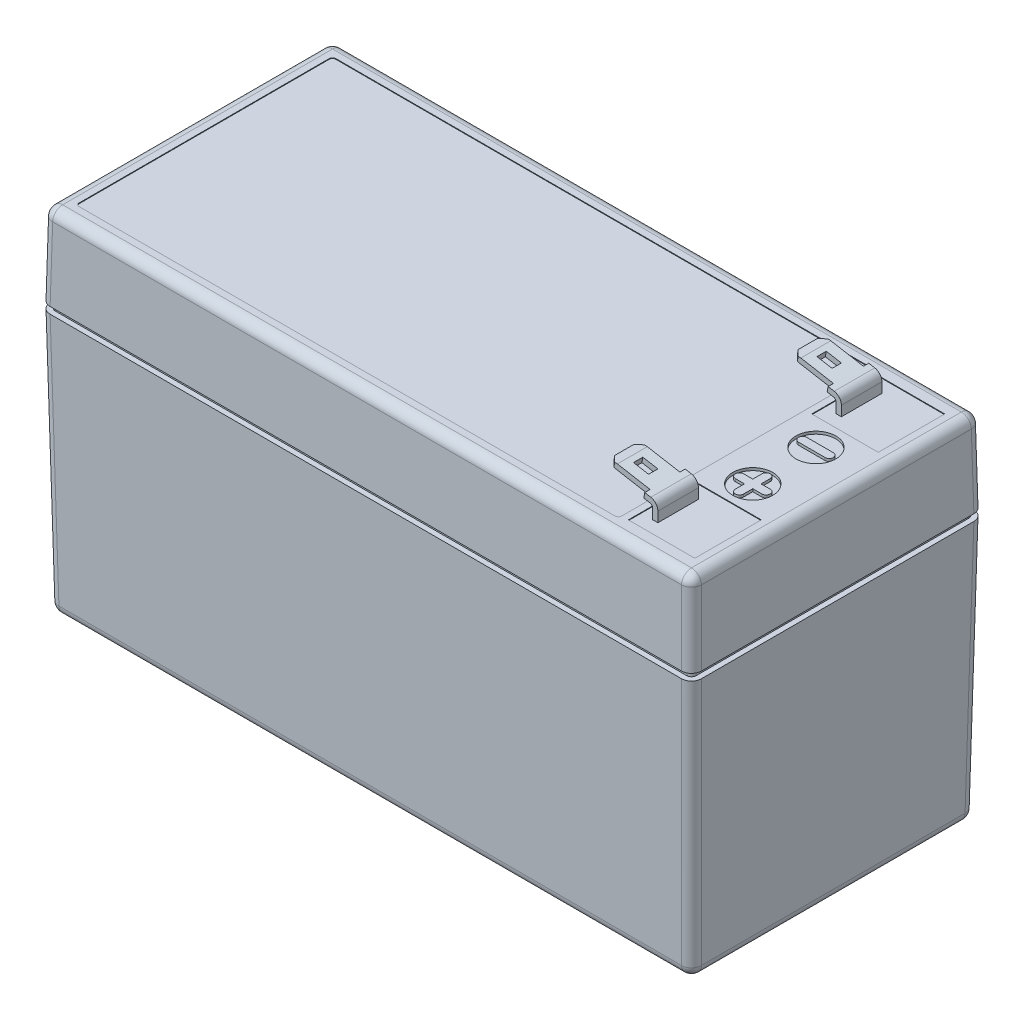
SolidWorks part; units mm, degrees
note: The reader was unsure of these and kept them because the rebuilt part matched: shared geometry of "Sketch4<3>".
ref_plane "Front Plane" through (0, 0, 0) normal (0, 0, 1) x (1, 0, 0)
ref_plane "Top Plane" through (0, 0, 0) normal (0, 1, 0) x (1, 0, 0)
ref_plane "Right Plane" through (0, 0, 0) normal (1, 0, 0) x (0, 0, -1)
sketch "Sketch1" plane through (0, 0, 0) normal (0, 1, 0) x (1, 0, 0)
  line L1 (-49, 22) -> (49, 22)
  line L2 (-49, 22) -> (-49, -22)
  line L3 (-49, -22) -> (49, -22)
  line L4 (49, 22) -> (49, -22)
  point P4 (-49, 0)
  point P6 (0, 22)
  dimension "D1" = 98
  dimension "D2" = 44
extrude "Extrude1" add sketch "Sketch1" along normal blind 13 draft 1 and the other way blind 40 draft 1
fillet "Fillet1" radius 1.5 16 edges at (48.7731, 13, 0) (-48.3018, -40, 0) (-48.6509, -20, 21.6509) (0, -40, -21.3018) (0, 13, -21.7731) (-48.6509, -20, -21.6509) (48.3018, -40, 0) (48.6509, -20, -21.6509) (0, -40, 21.3018) (48.6509, -20, 21.6509) (-48.7731, 13, 0) (0, 13, 21.7731) (-48.8865, 6.5, -21.8865) (48.8865, 6.5, -21.8865) (48.8865, 6.5, 21.8865) (-48.8865, 6.5, 21.8865)
sketch3d "3DSketch1"
  line L0 (-49, 0, -20.5002) -> (-49, 0, 20.5002) construction
  line L1 (47.5002, 0, -22) -> (-47.5002, 0, -22) construction
  line L2 (-47.5002, 0, 22) -> (47.5002, 0, 22) construction
  line L3 (49, 0, 20.5002) -> (49, 0, -20.5002) construction
  line L4 (-49, 0, -20.5002) -> (-49, 0, 20.5002)
  line L5 (47.5002, 0, -22) -> (-47.5002, 0, -22)
  line L6 (-47.5002, 0, 22) -> (47.5002, 0, 22)
  line L7 (49, 0, 20.5002) -> (49, 0, -20.5002)
  spline S0 degree 3 poles (-49, 0, 20.5002) (-49, 0, 21.3788) (-48.3788, 0, 22) (-47.5002, 0, 22) knots 0 0 0 0 1 1 1 1 weights 1 0.80481 0.80481 1 construction
  spline S1 degree 3 poles (-47.5002, 0, -22) (-48.3788, 0, -22) (-49, 0, -21.3788) (-49, 0, -20.5002) knots 0 0 0 0 1 1 1 1 weights 1 0.80481 0.80481 1 construction
  spline S2 degree 3 poles (49, 0, -20.5002) (49, 0, -21.3788) (48.3788, 0, -22) (47.5002, 0, -22) knots 0 0 0 0 1 1 1 1 weights 1 0.80481 0.80481 1 construction
  spline S3 degree 3 poles (47.5002, 0, 22) (48.3788, 0, 22) (49, 0, 21.3788) (49, 0, 20.5002) knots 0 0 0 0 1 1 1 1 weights 1 0.80481 0.80481 1 construction
  spline S4 degree 3 poles (-49, 0, 20.5002) (-49, 0, 21.3788) (-48.3788, 0, 22) (-47.5002, 0, 22) knots 0 0 0 0 1 1 1 1 weights 1 0.80481 0.80481 1
  spline S5 degree 3 poles (-47.5002, 0, -22) (-48.3788, 0, -22) (-49, 0, -21.3788) (-49, 0, -20.5002) knots 0 0 0 0 1 1 1 1 weights 1 0.80481 0.80481 1
  spline S6 degree 3 poles (49, 0, -20.5002) (49, 0, -21.3788) (48.3788, 0, -22) (47.5002, 0, -22) knots 0 0 0 0 1 1 1 1 weights 1 0.80481 0.80481 1
  spline S7 degree 3 poles (47.5002, 0, 22) (48.3788, 0, 22) (49, 0, 21.3788) (49, 0, 20.5002) knots 0 0 0 0 1 1 1 1 weights 1 0.80481 0.80481 1
sketch "Sketch3" plane through (0, 0, 0) normal (1, 0, 0) x (0, 0, -1)
  line L1 (22.4972, 0.5) -> (21.2, 0.5)
  line L2 (22.4972, 0.5) -> (22.4972, -0.5)
  line L3 (22.4972, -0.5) -> (21.2, -0.5)
  line L4 (21.2, 0.5) -> (21.2, -0.5)
  point P4 (21.2, 0)
  dimension "D1" = 1
  dimension "D2" = 0.8
sweep "Cut-Sweep1" cut profiles "Sketch3" path "3DSketch1"
sketch "Sketch4" plane through (0, -40, 0) normal (0, -1, 0) x (1, 0, 0)
  line L0 (46.8278, 19.8278) -> (-46.8278, 19.8278) construction
  line L1 (-44.6278, 17.6278) -> (-38.6278, 17.6278)
  line L2 (-44.6278, 17.6278) -> (-44.6278, 11.6278)
  line L3 (-44.6278, 11.6278) -> (-42.6278, 11.6278)
  line L4 (-38.6278, 17.6278) -> (-38.6278, 15.6278)
  line L5 (-42.6278, 15.6278) -> (-38.6278, 15.6278)
  line L6 (-42.6278, 15.6278) -> (-42.6278, 11.6278)
  line L7 (-46.8278, 19.8278) -> (-46.8278, -19.8278) construction
  line L8 (0, 11.6278) -> (0, -9.5326) construction
  line L9 (-20.3603, 0) -> (14.1633, 0) construction
  line L10 (42.6278, 15.6278) -> (42.6278, 11.6278)
  line L11 (42.6278, 15.6278) -> (38.6278, 15.6278)
  line L12 (38.6278, 17.6278) -> (38.6278, 15.6278)
  line L13 (44.6278, 11.6278) -> (42.6278, 11.6278)
  line L14 (44.6278, 17.6278) -> (44.6278, 11.6278)
  line L15 (44.6278, 17.6278) -> (38.6278, 17.6278)
  line L16 (44.6278, -17.6278) -> (38.6278, -17.6278)
  line L17 (44.6278, -17.6278) -> (44.6278, -11.6278)
  line L18 (44.6278, -11.6278) -> (42.6278, -11.6278)
  line L19 (38.6278, -17.6278) -> (38.6278, -15.6278)
  line L20 (42.6278, -15.6278) -> (38.6278, -15.6278)
  line L21 (42.6278, -15.6278) -> (42.6278, -11.6278)
  line L22 (-42.6278, -15.6278) -> (-42.6278, -11.6278)
  line L23 (-42.6278, -15.6278) -> (-38.6278, -15.6278)
  line L24 (-38.6278, -17.6278) -> (-38.6278, -15.6278)
  line L25 (-44.6278, -11.6278) -> (-42.6278, -11.6278)
  line L26 (-44.6278, -17.6278) -> (-44.6278, -11.6278)
  line L27 (-44.6278, -17.6278) -> (-38.6278, -17.6278)
  line L28 (-15, -1.75) -> (15, -1.75) construction
  line L29 (-18.5, 1.75) -> (-15, 1.75)
  line L30 (-18.5, 1.75) -> (-18.5, -1.75)
  line L31 (-18.5, -1.75) -> (-15, -1.75)
  line L32 (-15, 1.75) -> (-15, -1.75)
  line L33 (15, 1.75) -> (18.5, 1.75)
  line L34 (15, 1.75) -> (15, -1.75)
  line L35 (15, -1.75) -> (18.5, -1.75)
  line L36 (18.5, 1.75) -> (18.5, -1.75)
  point P41 (15, 0)
  point P42 (0, -1.75)
  dimension "D1" = 2
  dimension "D2" = 2
  dimension "D3" = 6
  dimension "D4" = 6
  dimension "D5" = 2.2
  dimension "D6" = 2.2
  dimension "D7" = 3.5
  dimension "D8" = 3.5
  dimension "D9" = 30
extrude "Extrude3" add sketch "Sketch4" along normal blind 0.3 contours L27 L24 L23 L22 L25 L26 | L3 L6 L5 L4 L1 L2 | L18 L21 L20 L19 L16 L17 | L15 L12 L11 L10 L13 L14
extrude "Cut-Extrude1" cut sketch "Sketch4<3>" against normal blind 0.5 contours L31 L32 L29 L30 | L35 L36 L33 L34
sketch "Sketch4<3>" plane through (0, -40, 0) normal (0, -1, 0) x (1, 0, 0) same geometry as "Sketch4"
sketch "Sketch5" plane through (0, 13, 0) normal (0, 1, 0) x (-1, 0, 0)
  line L0 (-47.299, -20.299) -> (47.299, -20.299) construction
  line L1 (46.299, 19.299) -> (-35.299, 19.299)
  line L2 (46.299, 19.299) -> (46.299, -19.299)
  line L3 (46.299, -19.299) -> (-35.299, -19.299)
  line L4 (-35.299, 19.299) -> (-35.299, -19.299)
  line L5 (47.299, 20.299) -> (-47.299, 20.299) construction
  line L6 (47.299, -20.299) -> (47.299, 20.299) construction
  line L7 (-47.299, 20.299) -> (-47.299, -20.299) construction
  dimension "D1" = 1
  dimension "D2" = 1
  dimension "D3" = 1
  dimension "D4" = 12
extrude "Cut-Extrude2" cut sketch "Sketch5" against normal blind 0.1
fillet "Fillet2" radius 0.5 4 edges at (35.299, 12.95, 19.299) (35.299, 12.95, -19.299) (-46.299, 12.95, 19.299) (-46.299, 12.95, -19.299)
sketch "Sketch6" plane through (0, 13, 0) normal (0, 1, 0) x (-1, 0, 0)
  line L0 (47.299, 20.299) -> (-47.299, 20.299) construction
  line L1 (-36.299, 18.799) -> (-46.299, 18.799)
  line L2 (-36.299, 18.799) -> (-36.299, 8.799)
  line L3 (-36.299, 8.799) -> (-46.299, 8.799)
  line L4 (-46.299, 18.799) -> (-46.299, 8.799)
  line L5 (-36.299, -8.799) -> (-46.299, -8.799)
  line L6 (-36.299, -8.799) -> (-36.299, -18.799)
  line L7 (-36.299, -18.799) -> (-46.299, -18.799)
  line L8 (-46.299, -8.799) -> (-46.299, -18.799)
  line L9 (-47.299, -20.299) -> (47.299, -20.299) construction
  line L10 (-47.299, 20.299) -> (-47.299, -20.299) construction
  dimension "D1" = 1.5
  dimension "D2" = 1.5
  dimension "D3" = 10
  dimension "D4" = 10
  dimension "D5" = 1
extrude "Cut-Extrude3" cut sketch "Sketch6" against normal blind 0.1
sketch "Sketch7" plane through (0, 0, 0) normal (0, 0, 1) x (1, 0, 0)
  line L0 (38.799, 11.5262) -> (38.799, 15.5)
  line L1 (47.299, 11.5262) -> (-47.299, 11.5262) construction
  line L2 (38.799, 15.5) -> (30.7236, 16.9239)
  line L3 (-47.299, 13) -> (47.299, 13) construction
  dimension "D1" = 2.5
  dimension "D2" = 2.5
  dimension "D3" = 8.2
  dimension "D4" = 100
extrude "Extrude-Thin1" add sketch "Sketch7" along normal blind 6.1 from offset 10.75 thin thin type one direction reverse wall 0.8
sketch "Sketch8" plane through (3.8206, 21.6676, 0) normal (0.1736, 0.9848, 0) x (-0.9848, 0.1736, 0)
  line L0 (-33.5075, 8.799) -> (-33.5075, 18.799) construction
  line L1 (-33.5075, 16.85) -> (-27.318, 16.85)
  line L2 (-33.5075, 16.85) -> (-33.5075, 16.05)
  line L3 (-33.5075, 16.05) -> (-27.318, 16.05)
  line L4 (-27.318, 16.85) -> (-27.318, 16.05)
  line L5 (-35.518, 16.85) -> (-27.318, 16.85) construction
  line L6 (-27.318, 16.85) -> (-27.318, 10.75) construction
  line L7 (-35.518, 10.75) -> (-27.318, 10.75) construction
  line L8 (-33.4901, 10.75) -> (-27.318, 10.75)
  line L9 (-33.4901, 10.75) -> (-33.4901, 11.55)
  line L10 (-33.4901, 11.55) -> (-27.318, 11.55)
  line L11 (-27.318, 10.75) -> (-27.318, 11.55)
  line L12 (-33.4901, 8.799) -> (-33.4901, 18.799) construction
  line L13 (-33.5075, 16.05) -> (-33.4988, 13.8) construction
  line L14 (-31.7062, 14.5) -> (-29.4062, 14.5)
  line L15 (-31.7062, 14.5) -> (-31.7062, 13.1)
  line L16 (-31.7062, 13.1) -> (-29.4062, 13.1)
  line L17 (-29.4062, 14.5) -> (-29.4062, 13.1)
  line L18 (-33.4988, 13.8) -> (-33.4901, 11.55) construction
  point P25 (-31.7062, 13.8)
  dimension "D1" = 0.8
  dimension "D2" = 0.8
  dimension "D3" = 2.3
  dimension "D4" = 1.4
extrude "Cut-Extrude4" cut sketch "Sketch8" against normal up to surface (0.8 mm away) up to face at (34.2919, 15.4824, 13.8)
mirror "Mirror1" about plane through (0, 0, 0) normal (0, 0, 1) of "Cut-Extrude4", "Extrude-Thin1"
fillet "Fillet3" radius 0.5 2 edges at (37.999, 14.8287, 13.8) (37.999, 14.8287, -13.8)
fillet "Fillet4" radius 1.3 2 edges at (38.799, 15.5, 13.8) (38.799, 15.5, -13.8)
chamfer "Chamfer1" distance 1.2 angle 5 4 edges at (30.7236, 16.9239, 13.8) (30.5847, 16.1361, 13.8) (30.5847, 16.1361, -13.8) (30.7236, 16.9239, -13.8)
chamfer "Chamfer2" distance 0.8 angle 45 4 edges at (30.6542, 16.53, 16.05) (30.6542, 16.53, 11.55) (30.6542, 16.53, -11.55) (30.6542, 16.53, -16.05)
sketch "Sketch9" plane through (0, 13, 0) normal (0, 1, 0) x (-1, 0, 0)
  line L0 (-40.9694, -4.75) -> (-40.9694, 4.75) construction
  line L1 (-43.7834, 0) -> (-46.2281, 0) construction
  line L14 (-41.5944, 6.75) -> (-41.5944, 2.75)
  line L15 (-40.3444, 2.75) -> (-41.5944, 2.75)
  line L16 (-40.3444, 6.75) -> (-40.3444, 2.75)
  line L17 (-40.3444, 6.75) -> (-41.5944, 6.75)
  line L18 (-42.9694, 5.375) -> (-42.9694, 4.125)
  line L19 (-38.9694, 4.125) -> (-42.9694, 4.125)
  line L20 (-38.9694, 5.375) -> (-38.9694, 4.125)
  line L21 (-38.9694, 5.375) -> (-42.9694, 5.375)
  line L22 (-42.9694, -4.125) -> (-42.9694, -5.375)
  line L23 (-38.9694, -5.375) -> (-42.9694, -5.375)
  line L24 (-38.9694, -4.125) -> (-38.9694, -5.375)
  line L25 (-38.9694, -4.125) -> (-42.9694, -4.125)
  circle A8 centre (-40.9694, 2.75) radius 0.625
  circle A9 centre (-40.9694, 6.75) radius 0.625
  circle A10 centre (-42.9694, 4.75) radius 0.625
  circle A11 centre (-38.9694, 4.75) radius 0.625
  circle A12 centre (-42.9694, -4.75) radius 0.625
  circle A13 centre (-38.9694, -4.75) radius 0.625
  circle A14 centre (-40.9694, -4.75) radius 3
  circle A15 centre (-40.9694, 4.75) radius 3
  point P4 (-40.9694, 0)
  dimension "D2" = 9.5
extrude "Cut-Extrude5" cut sketch "Sketch9" against normal blind 0.4
ref_plane "Plane1" through (0, -40.3, 0) normal (0, 1, 0) x (-1, 0, 0)
sketch "Component_Outline" plane through (0, -40.3, 0) normal (0, 1, 0) x (-1, 0, 0)
  line L0 (47.4915, 21.9913) -> (-47.4915, 21.9913) construction
  line L1 (48.9913, 21.9913) -> (-48.9913, 21.9913)
  line L2 (48.9913, 21.9913) -> (48.9913, -21.9913)
  line L3 (48.9913, -21.9913) -> (-48.9913, -21.9913)
  line L4 (-48.9913, 21.9913) -> (-48.9913, -21.9913)
  line L5 (48.9913, -20.4915) -> (48.9913, 20.4915) construction
  line L6 (-47.4915, -21.9913) -> (47.4915, -21.9913) construction
  line L7 (-48.9913, 20.4915) -> (-48.9913, -20.4915) construction
  point P12 (0, 0)
